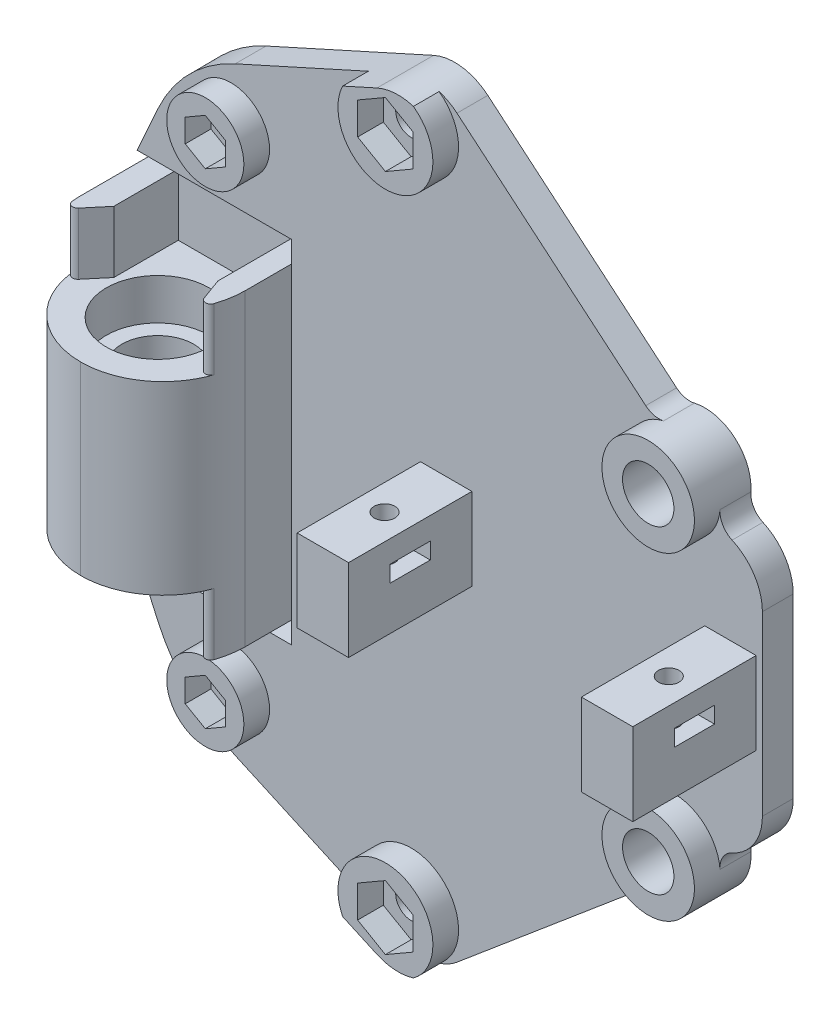
SolidWorks part; units mm, degrees
ref_plane "Alzado" through (0, 0, 0) normal (0, 0, 1) x (1, 0, 0)
ref_plane "Planta" through (0, 0, 0) normal (0, 1, 0) x (1, 0, 0)
ref_plane "Vista lateral" through (0, 0, 0) normal (1, 0, 0) x (0, 0, -1)
sketch "Croquis2" plane through (0, 0, 0) normal (0, 0, 1) x (1, 0, 0)
  line L0 (-10.8224, 56.7562) -> (13.1094, 21.0366)
  line L1 (-11.5974, 58.2365) -> (-14.2242, 64.9243)
  line L2 (-14.2242, 64.9243) -> (-52.0695, 47.8283)
  line L3 (-53.0688, 45.1822) -> (-51.6513, 42.0443)
  line L4 (13.1094, 21.0366) -> (-53.0688, 21.0366) construction
  line L5 (-53.0688, -3.109) -> (-51.6513, 0.0289)
  line L6 (-14.2242, -22.8511) -> (-52.0695, -5.755)
  line L7 (-11.5974, -16.1633) -> (-14.2242, -22.8511)
  line L8 (-10.8224, -14.683) -> (13.1094, 21.0366)
  circle A0 centre (-29.7722, 54.0212) radius 1.5
  circle A1 centre (-47.2934, 44.6229) radius 1
  circle A2 centre (-19.6168, 40.1285) radius 2
  circle A3 centre (-4.2087, 36.5366) radius 2.3724
  arc A4 (-52.0695, 47.8283) -> (-53.0688, 45.1822) centre (-51.2461, 46.0056) ccw
  arc A5 (-51.6513, 42.0443) -> (-48.9209, 41.0856) centre (-49.8287, 42.8677) ccw
  arc A6 (-48.9209, 41.0856) -> (-48.9209, 0.9876) centre (-38.7087, 21.0366) cw
  arc A7 (-11.5974, 58.2365) -> (-10.8224, 56.7562) centre (-4.3839, 61.0699) ccw
  arc A8 (-11.5974, -16.1633) -> (-10.8224, -14.683) centre (-4.3839, -18.9967) cw
  arc A9 (-51.6513, 0.0289) -> (-48.9209, 0.9876) centre (-49.8287, -0.7945) cw
  arc A10 (-52.0695, -5.755) -> (-53.0688, -3.109) centre (-51.2461, -3.9324) cw
  circle A11 centre (-4.2087, 5.5366) radius 2.3724
  circle A12 centre (-19.6168, 1.9447) radius 2
  circle A13 centre (-47.2934, -2.5497) radius 1
  circle A14 centre (-29.7722, -11.948) radius 1.5
sketch "Croquis3" plane through (0, 0, 0) normal (0, 0, 1) x (1, 0, 0)
  line L0 (-6.9479, 41.3425) -> (-27.7187, 58.8284)
  line L1 (-14.2242, 64.9243) -> (-52.0695, 47.8283) construction
  line L2 (-27.7187, 58.8284) -> (-52.0695, 47.8283)
  line L3 (-29.7722, 54.0212) -> (-26.5521, 57.8462) construction
  line L6 (13.1094, 21.0366) -> (-53.0688, 21.0366) construction
  line L7 (-53.0688, 21.0366) -> (4.3995, 21.0366) construction
  line L8 (-29.7722, -11.948) -> (-26.5521, -15.773) construction
  line L9 (-27.7187, -16.7552) -> (-52.0695, -5.755)
  line L10 (-6.9479, 0.7307) -> (-27.7187, -16.7552)
  line L12 (2.272, 34.0366) -> (4.3995, 34.0366)
  line L13 (-10.8224, 56.7562) -> (13.1094, 21.0366) construction
  line L15 (-10.8224, -14.683) -> (13.1094, 21.0366) construction
  line L19 (4.3995, 34.0366) -> (4.3995, 8.0366)
  line L20 (-53.0688, 21.0366) -> (-64.0688, 21.0366) construction
  line L21 (-52.0695, -5.755) -> (-64.0688, 21.0366)
  line L22 (-64.0688, 21.0366) -> (-52.0695, 47.8283)
  line L23 (2.272, 8.0366) -> (4.3995, 8.0366)
  arc A2 (0.2779, 36.1905) -> (-5.2133, 40.923) centre (-4.2087, 36.5366) ccw
  circle A3 centre (-4.2087, 36.5366) radius 2.5
  circle A4 centre (-29.7722, 54.0212) radius 1.5
  circle A6 centre (-47.2934, 44.6229) radius 1
  circle A7 centre (-4.2087, 5.5366) radius 2.5
  circle A8 centre (-47.2934, -2.5497) radius 1
  circle A10 centre (-29.7722, -11.948) radius 1.5
  arc A12 (0.2779, 5.8828) -> (-5.2133, 1.1502) centre (-4.2087, 5.5366) cw
  arc A13 (-5.2133, 1.1502) -> (-6.9479, 0.7307) centre (-5.6598, -0.7993) ccw
  arc A14 (0.2779, 5.8828) -> (2.272, 8.0366) centre (2.272, 6.0366) cw
  arc A15 (-5.2133, 40.923) -> (-6.9479, 41.3425) centre (-5.6598, 42.8726) cw
  arc A16 (0.2779, 36.1905) -> (2.272, 34.0366) centre (2.272, 36.0366) ccw
  point P37 (-6.0932, 1.4502)
  point P45 (-0.4671, 8.0366)
  point P48 (-6.0932, 40.623)
  point P51 (-0.4671, 34.0366)
  dimension "D1" = 2
  dimension "D2" = 3
  dimension "D4" = 2
  dimension "D5" = 11
  dimension "D6" = 9
  dimension "D3" = 5
extrude "Saliente-Extruir1" add sketch "Croquis3" against normal blind 3
sketch "Croquis4" plane through (0, 0, 0) normal (0, 0, 1) x (1, 0, 0)
  line L0 (-23.8587, 25.6616) -> (-23.8587, 9.9116)
  line L1 (-23.8587, 9.9116) -> (-1.2087, 9.9116)
  line L2 (-1.2087, 9.9116) -> (-1.2087, 25.6616)
  line L3 (-1.2087, 25.6616) -> (3.7913, 25.6616)
  line L4 (3.7913, 25.6616) -> (3.7913, 28.1616)
  line L5 (3.7913, 28.1616) -> (-1.2087, 28.1616)
  line L6 (-1.2087, 28.1616) -> (-1.2087, 32.1616)
  line L7 (-1.2087, 32.1616) -> (-8.2087, 32.1616)
  line L8 (-8.2087, 32.1616) -> (-23.8587, 32.1616)
  line L9 (-23.8587, 32.1616) -> (-23.8587, 28.1616)
  line L10 (-23.8587, 28.1616) -> (-28.8587, 28.1616)
  line L11 (-28.8587, 28.1616) -> (-28.8587, 25.6616)
  line L12 (-28.8587, 25.6616) -> (-23.8587, 25.6616)
  line L13 (2.272, 8.0366) -> (4.3995, 8.0366) construction
  line L14 (-12.5337, 9.9116) -> (-12.5337, 32.1616) construction
  line L16 (-6.7087, 36.5366) -> (-6.7087, 5.5366) construction
  circle A2 centre (-4.2087, 5.5366) radius 2.5 construction
  circle A3 centre (-4.2087, 36.5366) radius 2.5 construction
  dimension "D1" = 22.25
  dimension "D2" = 22.65
  dimension "D3" = 5
  dimension "D4" = 2.5
  dimension "D5" = 5
  dimension "D6" = 4
  dimension "D7" = 22.65
  dimension "D8" = 4
  dimension "D9" = 5
  dimension "D10" = 2.5
  dimension "D11" = 5
  dimension "D12" = 15.75
  dimension "D13" = 7
  dimension "D14" = 1.5
sketch "Croquis5" plane through (0, 0, 0) normal (0, 0, 1) x (1, 0, 0)
  line L0 (-28.8587, 25.6616) -> (-23.8587, 25.6616)
  line L1 (-28.8587, 25.6616) -> (-23.8587, 25.6616) construction
  line L2 (-23.8587, 25.6616) -> (-23.8587, 17.6616)
  line L3 (-23.8587, 17.6616) -> (-28.8587, 17.6616)
  line L4 (-28.8587, 17.6616) -> (-28.8587, 25.6616)
  line L5 (-12.5337, 32.1616) -> (-12.5337, 9.9116) construction
  line L6 (3.7913, 17.6616) -> (3.7913, 25.6616)
  line L7 (-1.2087, 17.6616) -> (3.7913, 17.6616)
  line L8 (-1.2087, 25.6616) -> (-1.2087, 17.6616)
  line L9 (3.7913, 25.6616) -> (-1.2087, 25.6616)
  dimension "D1" = 5
  dimension "D2" = 8
extrude "Saliente-Extruir2" add sketch "Croquis5" along normal blind 12
sketch "Croquis6" plane through (0, 25.6616, 0) normal (0, 1, 0) x (1, 0, 0)
  line L0 (-1.2087, -12) -> (-23.8587, -12) construction
  line L1 (-12.5337, -12) -> (-12.5337, -6.075) construction
  line L2 (-28.8587, -12) -> (-28.8587, 0) construction
  line L3 (-23.8587, -12) -> (-28.8587, -12) construction
  circle A0 centre (-26.3587, -6) radius 1
  circle A1 centre (1.2913, -6) radius 1
  point P16 (-28.8587, -6)
  point P19 (-26.3587, -12)
  dimension "D1" = 2
extrude "Cortar-Extruir1" cut sketch "Croquis6" against normal blind 7
sketch "Croquis7" plane through (0, 0, 0) normal (0, 0, 1) x (1, 0, 0)
  line L1 (-59.0695, 30.0366) -> (-43.0695, 30.0366)
  line L2 (-59.0695, 30.0366) -> (-59.0695, 12.0366)
  line L3 (-59.0695, 12.0366) -> (-43.0695, 12.0366)
  line L4 (-43.0695, 30.0366) -> (-43.0695, 12.0366)
  line L5 (-52.0695, 21.0366) -> (-28.8587, 21.0366) construction
  line L6 (-28.8587, 25.6616) -> (-28.8587, 17.6616) construction
  line L7 (-52.0695, -5.755) -> (-52.0695, 47.8283) construction
  point P4 (-43.0695, 21.0366)
  dimension "D1" = 18
  dimension "D2" = 16
  dimension "D4" = 7
ref_plane "Plano1" through (0, 21.0366, 0) normal (0, -1, 0) x (-1, 0, 0)
sketch "Croquis10" plane through (0, 0, 0) normal (0, 0, 1) x (1, 0, 0)
  line L0 (-47.2934, 42.3712) -> (-47.2934, 40.8712) construction
  line L1 (-47.2934, 42.3712) -> (-45.3434, 43.4971)
  line L2 (-45.3434, 43.4971) -> (-45.3434, 45.7487)
  line L3 (-45.3434, 45.7487) -> (-47.2934, 46.8746)
  line L4 (-47.2934, 46.8746) -> (-49.2434, 45.7487)
  line L5 (-49.2434, 45.7487) -> (-49.2434, 43.4971)
  line L6 (-49.2434, 43.4971) -> (-47.2934, 42.3712)
  line L7 (-29.7722, 50.9035) -> (-27.0722, 52.4624)
  line L8 (-27.0722, 52.4624) -> (-27.0722, 55.58)
  line L9 (-27.0722, 55.58) -> (-29.7722, 57.1389)
  line L10 (-29.7722, 57.1389) -> (-32.4722, 55.58)
  line L11 (-32.4722, 55.58) -> (-32.4722, 52.4624)
  line L12 (-32.4722, 52.4624) -> (-29.7722, 50.9035)
  line L13 (-29.7722, 50.9035) -> (-29.7722, 49.4035) construction
  line L14 (-28.5207, 58.4661) -> (-33.9347, 56.0204)
  line L15 (-27.7187, 58.8284) -> (-52.0695, 47.8283) construction
  circle A7 centre (-47.2934, 44.6229) radius 1.95 construction
  circle A8 centre (-29.7722, 54.0212) radius 2.7 construction
  arc A9 (-33.9347, 56.0204) -> (-28.5207, 58.4661) centre (-29.7722, 54.0212) ccw
  circle A10 centre (-47.2934, 44.6229) radius 3.7517
  circle A11 centre (-4.2087, 36.5366) radius 2.5
  circle A12 centre (-4.2087, 36.5366) radius 4.5
  circle A13 centre (-4.2087, 36.5366) radius 2.5 construction
  arc A14 (0.2779, 36.1905) -> (-5.2133, 40.923) centre (-4.2087, 36.5366) ccw construction
  dimension "D1" = 3.9
  dimension "D2" = 5.4
  dimension "D3" = 1.5
  dimension "D4" = 1.5
extrude "Saliente-Extruir4" add sketch "Croquis10" along normal blind 2.5
mirror "Simetría2" about plane through (0, 21.0366, 0) normal (0, -1, 0) of "Saliente-Extruir4"
fillet "Redondeo4" radius 15 3 edges at (-52.0695, 47.8283, -1.5) (-52.0695, -5.755, -1.5) (-64.0688, 21.0366, -1.5)
fillet "Redondeo5" radius 5 4 edges at (4.3995, 34.0366, -1.5) (-27.7187, 58.8284, -1.5) (-27.7187, -16.7552, -1.5) (4.3995, 8.0366, -1.5)
sketch "Croquis14" plane through (0, 0, -3) normal (0, 0, -1) x (-1, 0, 0)
  line L0 (62.6331, 21.0366) -> (47.6331, 21.0366) construction
  line L1 (53.0688, -3.109) -> (51.6513, 0.0289) construction
  line L2 (51.6513, 42.0443) -> (53.0688, 45.1822) construction
  line L3 (53.0183, -2.9973) -> (51.6513, 0.0289)
  line L4 (51.6513, 42.0443) -> (53.0183, 45.0705)
  line L5 (61.3228, 14.9053) -> (54.3963, -0.5598) construction
  line L6 (54.3963, 42.6331) -> (61.3228, 27.1679) construction
  line L7 (61.3228, 14.9053) -> (54.3963, -0.5598)
  line L8 (54.3963, 42.6331) -> (61.3228, 27.1679)
  arc A0 (61.3228, 14.9053) -> (61.3228, 27.1679) centre (47.6331, 21.0366) ccw construction
  arc A1 (51.6513, 0.0289) -> (48.9209, 0.9876) centre (49.8287, -0.7945) ccw construction
  arc A2 (48.9209, 41.0856) -> (51.6513, 42.0443) centre (49.8287, 42.8677) ccw construction
  arc A3 (48.9209, 41.0856) -> (48.9209, 0.9876) centre (38.7087, 21.0366) ccw construction
  arc A4 (51.6513, 0.0289) -> (48.9209, 0.9876) centre (49.8287, -0.7945) ccw
  arc A5 (48.9209, 41.0856) -> (51.6513, 42.0443) centre (49.8287, 42.8677) ccw
  arc A6 (48.9209, 41.0856) -> (48.9209, 0.9876) centre (38.7087, 21.0366) ccw
  arc A8 (46.8818, -8.0985) -> (54.3963, -0.5598) centre (40.7066, 5.5714) ccw construction
  arc A9 (54.3963, 42.6331) -> (46.8818, 50.1717) centre (40.7066, 36.5018) ccw construction
  arc A10 (53.0183, -2.9973) -> (54.3963, -0.5598) centre (40.7066, 5.5714) ccw
  arc A11 (54.3963, 42.6331) -> (53.0183, 45.0705) centre (40.7066, 36.5018) ccw
  arc A12 (61.3228, 14.9053) -> (61.3228, 27.1679) centre (47.6331, 21.0366) ccw
extrude "Saliente-Extruir6" add sketch "Croquis14" along normal blind 2.5
sketch "Croquis15" plane through (0, 0, 0) normal (0, 0, 1) x (1, 0, 0)
  line L0 (-62.6331, 21.0366) -> (-47.6331, 21.0366) construction
  line L1 (-61.3228, 14.9053) -> (-56.4178, 3.9536)
  line L2 (-61.3228, 14.9053) -> (-54.3963, -0.5598) construction
  line L3 (-56.4178, 3.9536) -> (-41.4178, 3.9536)
  line L4 (-41.4178, 3.9536) -> (-41.4178, 38.1196)
  line L5 (-56.4178, 38.1196) -> (-41.4178, 38.1196)
  line L6 (-61.3228, 27.1679) -> (-56.4178, 38.1196)
  arc A0 (-61.3228, 14.9053) -> (-61.3228, 27.1679) centre (-47.6331, 21.0366) cw
  point P14 (-41.4178, 21.0366)
  dimension "D1" = 12
  dimension "D2" = 15
extrude "Cortar-Extruir5" cut sketch "Croquis15" against normal blind 2.5
sketch "Croquis16" plane through (0, 0, -2.5) normal (0, 0, 1) x (1, 0, 0)
  line L1 (-57.4178, 30.0366) -> (-41.4178, 30.0366)
  line L2 (-57.4178, 30.0366) -> (-57.4178, 12.0366)
  line L3 (-57.4178, 12.0366) -> (-41.4178, 12.0366)
  line L4 (-41.4178, 30.0366) -> (-41.4178, 12.0366)
  line L5 (-41.4178, 3.9536) -> (-41.4178, 38.1196) construction
  point P4 (-41.4178, 21.0366)
  point P7 (-41.4178, 21.0366)
  dimension "D1" = 16
  dimension "D2" = 18
extrude "Saliente-Extruir7" add sketch "Croquis16" along normal blind 15
sketch "Croquis8" plane through (0, 12.0366, 0) normal (0, -1, 0) x (1, 0, 0)
  line L0 (-57.4178, 5) -> (-49.4178, 5) construction
  line L2 (-49.4178, 5) -> (-49.4178, -2.5) construction
  line L4 (-57.4178, -2.5) -> (-41.4178, -2.5) construction
  line L5 (-57.4178, 12.5) -> (-57.4178, -2.5) construction
  circle A0 centre (-49.4178, 5) radius 5
  dimension "D1" = 10
extrude "Cortar-Extruir2" cut sketch "Croquis8" against normal blind 4
extrude "Cortar-Extruir3" cut sketch "Croquis8<2>" along normal blind 4 from surface starting at face at (-47.8178, 30.0366, 4)
sketch "Croquis8<2>" plane through (0, 12.0366, 0) normal (0, -1, 0) x (1, 0, 0) same geometry as "Croquis8"
sketch "Croquis12" plane through (0, 16.0366, 0) normal (0, -1, 0) x (1, 0, 0)
  circle A0 centre (-49.4178, 5) radius 3.5
  dimension "D1" = 7
extrude "Cortar-Extruir4" cut sketch "Croquis12" against normal up to surface (10 mm away) up to face at (-49.4178, 26.0366, 0)
fillet "Redondeo6" radius 8 2 edges at (-41.4178, 21.0366, 12.5) (-57.4178, 21.0366, 12.5)
sketch "Croquis17" plane through (0, 12.0366, 0) normal (0, -1, 0) x (1, 0, 0)
  line L0 (-49.4178, 12.5) -> (-49.4178, 0) construction
  line L1 (-49.4178, 0) -> (-56.428, 8.3545) construction
  line L2 (-49.4178, 0) -> (-45.2864, 11.3507) construction
  line L3 (-49.4178, 5) -> (-59.0575, 16.4882) construction
  line L5 (-54.9178, 3.776) -> (-54.9178, -2.5)
  line L6 (-57.4178, -2.5) -> (-41.4178, -2.5) construction
  line L7 (-57.4178, 4.5) -> (-57.4178, -2.5)
  line L8 (-57.4178, -2.5) -> (-54.9178, -2.5)
  line L9 (-49.4178, 5) -> (-45.2569, 16.4318) construction
  line L10 (-45.2569, 16.4318) -> (-40.0886, 14.5507) construction
  line L11 (-40.0886, 14.5507) -> (-42.3694, 8.2843) construction
  line L12 (-41.4178, 4.5) -> (-41.4178, -2.5)
  line L13 (-41.4178, -2.5) -> (-43.5648, -2.5)
  line L14 (-42.3694, 8.2843) -> (-43.5648, 5)
  line L15 (-43.5648, 5) -> (-43.5648, -2.5)
  line L16 (-59.0575, 16.4882) -> (-62.8877, 13.2742) construction
  line L17 (-62.8877, 13.2742) -> (-49.6515, -2.5) construction
  line L18 (-57.173, 6.4637) -> (-54.9178, 3.776)
  circle A0 centre (-49.4178, 5) radius 5 construction
  arc A1 (-49.4178, 12.5) -> (-57.4178, 4.5) centre (-49.4178, 4.5) ccw construction
  arc A2 (-41.4178, 4.5) -> (-49.4178, 12.5) centre (-49.4178, 4.5) ccw construction
  arc A3 (-42.3694, 8.2843) -> (-41.4178, 4.5) centre (-49.4178, 4.5) cw
  arc A4 (-57.4178, 4.5) -> (-57.173, 6.4637) centre (-49.4178, 4.5) cw
  dimension "D1" = 40
  dimension "D2" = 20
  dimension "D3" = 2.5
  dimension "D4" = 5.5
  dimension "D5" = 5
extrude "Saliente-Extruir8" add sketch "Croquis17" along normal blind 6
fillet "Redondeo10" radius 0.5 2 edges at (-42.3694, 9.0366, 8.2843) (-57.173, 9.0366, 6.4637)
mirror "Simetría3" about plane through (0, 21.0366, 0) normal (0, -1, 0) of "Redondeo10", "Saliente-Extruir8"
sketch "Croquis18" plane through (-28.8587, 0, 0) normal (-1, 0, 0) x (0, 0, 1)
  line L0 (12, 25.6616) -> (0, 25.6616) construction
  line L1 (7.95, 23.5058) -> (4.05, 23.5058)
  line L2 (7.95, 23.5058) -> (7.95, 21.9058)
  line L3 (7.95, 21.9058) -> (4.05, 21.9058)
  line L4 (4.05, 23.5058) -> (4.05, 21.9058)
  point P4 (6, 23.5058)
  point P7 (6, 25.6616)
  dimension "D1" = 3.9
  dimension "D2" = 1.6
extrude "Cortar-Extruir6" cut sketch "Croquis18" against normal up to vertex (32.65 mm away) up to point (3.7913, 25.6616, 12)
